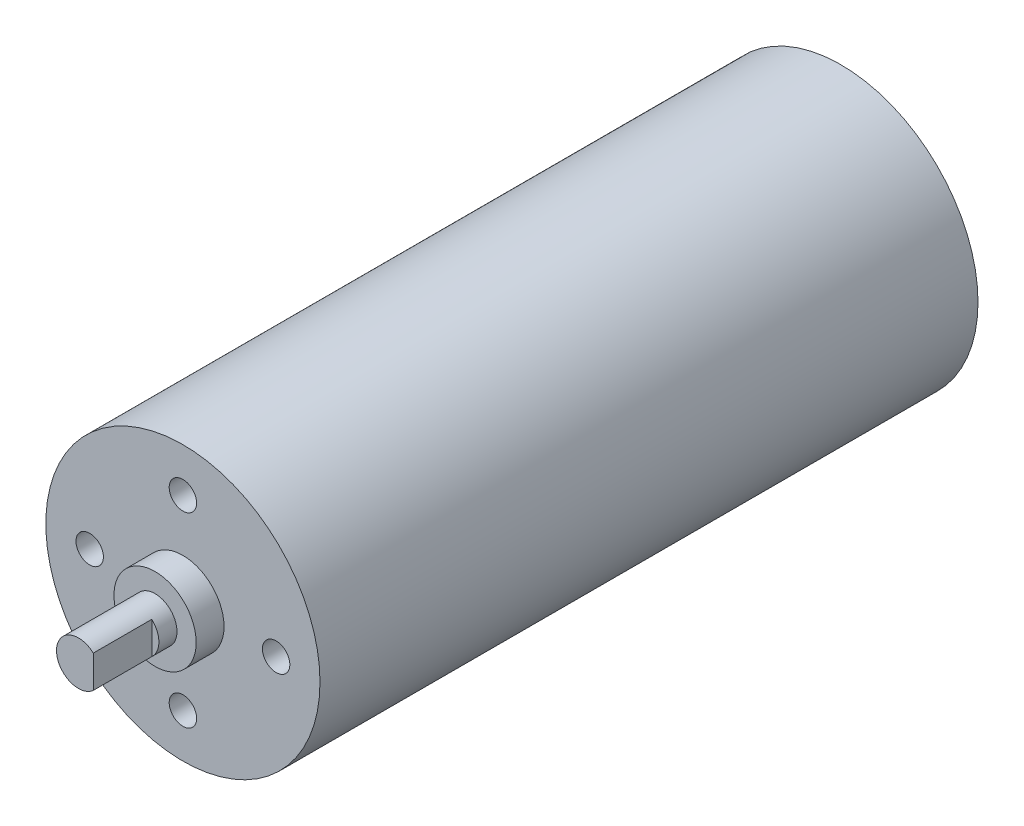
SolidWorks part; units mm, degrees
ref_plane "Front Plane" through (0, 0, 0) normal (0, 0, 1) x (1, 0, 0)
ref_plane "Top Plane" through (0, 0, 0) normal (0, 1, 0) x (1, 0, 0)
ref_plane "Right Plane" through (0, 0, 0) normal (1, 0, 0) x (0, 0, -1)
sketch "Specs" plane through (0, 0, 0) normal (0, 0, 1) x (1, 0, 0)
  line L0 (0, 12.5) -> (60, 12.5)
  line L1 (-8.5, 0) -> (8.5, 0) construction
  line L2 (0, -12.5) -> (60, -12.5)
  line L3 (-9.525, 2) -> (0, 2)
  line L4 (0, 8.5) -> (0, -8.5) construction
  line L6 (-9.525, -2) -> (0, -2)
  circle A0 centre (0, 0) radius 12.5
  circle A1 centre (60, 0) radius 12.5
  circle A2 centre (0, 0) radius 2
  circle A3 centre (0, 0) radius 3.75 construction
  circle A4 centre (0, 8.5) radius 1.65 construction
  circle A5 centre (8.5, 0) radius 1.65 construction
  circle A6 centre (0, -8.5) radius 1.65 construction
  circle A7 centre (-8.5, 0) radius 1.65 construction
  circle A8 centre (-9.525, 0) radius 2
  dimension "D2" = 3.3
  dimension "D3" = 7.5
  dimension "D4" = 4
  dimension "D5" = 25
  dimension "D1" = 17
  dimension "D6" = 60
  dimension "D7" = 9.525
sketch "Sketch1" plane through (0, 0, 0) normal (0, 0, 1) x (1, 0, 0)
  circle A0 centre (0, 0) radius 12.5
  circle A1 centre (0, 0) radius 12.5 construction
extrude "Boss-Extrude1" add sketch "Sketch1" against normal blind 60
sketch "Sketch4" plane through (0, 0, 0) normal (0, 0, 1) x (1, 0, 0)
  circle A0 centre (0, 0) radius 2
extrude "Boss-Extrude3" add sketch "Sketch4" along normal blind 9.525
sketch "Sketch5" plane through (0, 0, 0) normal (0, 0, 1) x (1, 0, 0)
  circle A0 centre (0, 0) radius 3.75
extrude "Boss-Extrude4" add sketch "Sketch5" along normal blind 2.54
sketch "Sketch6" plane through (0, 0, 9.525) normal (0, 0, 1) x (1, 0, 0)
  line L0 (1.3528, 1.4731) -> (1.3528, -1.4731)
  circle A0 centre (0, 0) radius 2 construction
  arc A1 (1.3528, 1.4731) -> (1.3528, -1.4731) centre (0, 0) cw
extrude "Cut-Extrude2" cut sketch "Sketch6" against normal blind 5.334
hole_wizard "Tap Drill for M3x0.5 Tap1" positions "Sketch8" profile "Sketch7" hole size "M3x0.5" standard "ANSI Metric"
sketch "Sketch8" plane through (0, 0, 0) normal (0, 0, 1) x (1, 0, 0)
  point P0 (0, 8.5)
  point P3 (8.5, 0)
  point P6 (0, -8.5)
  point P9 (-8.5, 0)
sketch "Sketch7" plane through (0, 8.5, 0) normal (1, 0, 0) x (0, -1, 0)
  line L0 (0, 0) -> (0, 10.7511)
  line L1 (0, 10.7511) -> (1.25, 10)
  line L2 (1.25, 10) -> (1.25, 0)
  line L5 (1.25, 0) -> (0, 0)
  line L10 (0, 10.7511) -> (-1.25, 10) construction
  line L11 (0, -6.35) -> (0, 107.95) construction
  dimension "Hole Dia." = 2.5
  dimension "Hole Depth" = 10
  dimension "Drill Angle" = 118
equation "\"D1@Boss-Extrude1\"=\"D6@Specs\""
equation "\"D1@Boss-Extrude3\"=\"D7@Specs\""
